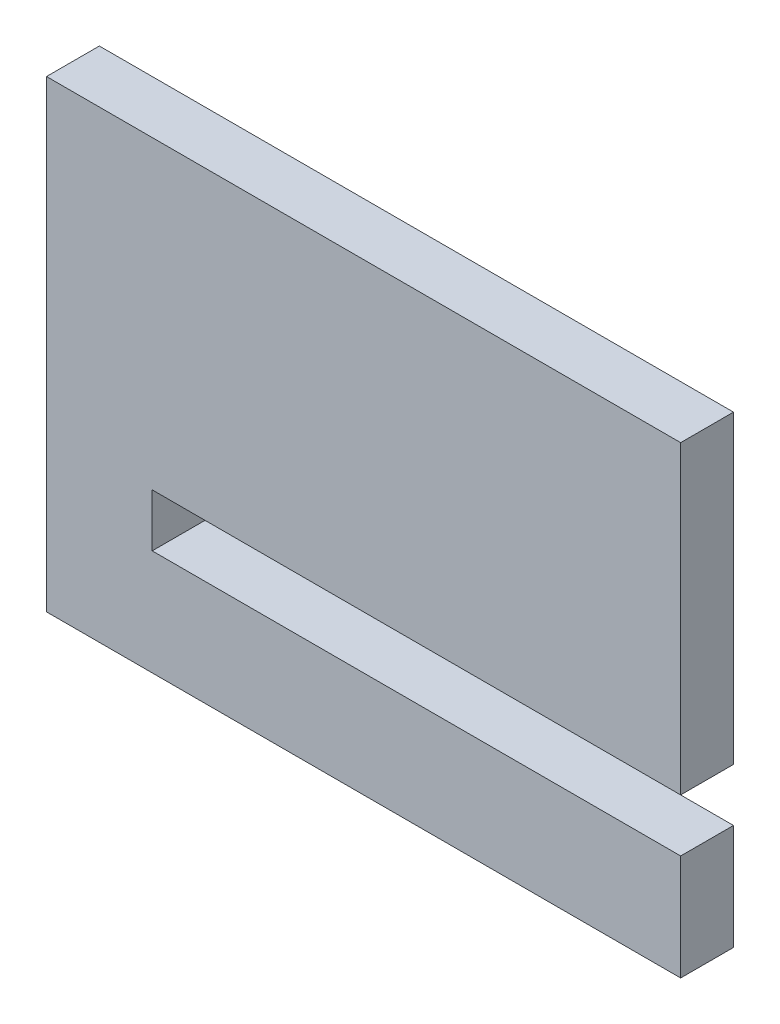
SolidWorks part; units mm, degrees
material "Pino"
ref_plane "Alzado" through (0, 0, 0) normal (0, 0, 1) x (1, 0, 0)
ref_plane "Planta" through (0, 0, 0) normal (0, 1, 0) x (1, 0, 0)
ref_plane "Vista lateral" through (0, 0, 0) normal (1, 0, 0) x (0, 0, -1)
sketch "Croquis1" plane through (0, 0, 0) normal (0, 1, 0) x (1, 0, 0)
  line L1 (-152.4, -12.7) -> (152.4, -12.7)
  line L2 (-152.4, -12.7) -> (-152.4, 12.7)
  line L3 (-152.4, 12.7) -> (152.4, 12.7)
  line L4 (152.4, -12.7) -> (152.4, 12.7)
  line L5 (-152.4, -12.7) -> (152.4, 12.7) construction
  line L6 (-152.4, 12.7) -> (152.4, -12.7) construction
  point P0 (0, 0)
  dimension "D1" = 25.4
  dimension "D2" = 304.8
extrude "Saliente-Extruir1" add sketch "Croquis1" along normal blind 50.8
sketch "Sketch1" plane through (0, 0, 12.7) normal (0, 0, 1) x (1, 0, 0)
  line L0 (-152.4, 50.8) -> (-152.4, 152.4)
  line L1 (-152.4, 152.4) -> (-101.6, 152.4)
  line L2 (-101.6, 152.4) -> (-101.6, 50.8)
  line L3 (-152.4, 50.8) -> (152.4, 50.8) construction
  line L4 (-101.6, 50.8) -> (-152.4, 50.8)
  dimension "D1" = 50.8
  dimension "D2" = 101.6
extrude "Boss-Extrude1" add sketch "Sketch1" against normal up to surface (25.4 mm away) up to face at (0, 25.4, -12.7)
sketch "Sketch2" plane through (0, 0, 12.7) normal (0, 0, 1) x (1, 0, 0)
  line L4 (152.4, 431.8) -> (152.4, -25.4) construction
  line L5 (152.4, 222.85) -> (152.4, 76.2)
  line L9 (-101.6, 76.2) -> (152.4, 76.2)
  line L10 (-101.6, 76.2) -> (152.4, 76.2) construction
  line L11 (152.4, 222.85) -> (-152.4, 222.85)
  line L12 (-152.4, 431.8) -> (-152.4, -25.4) construction
  line L13 (-152.4, 222.85) -> (-152.4, 152.4)
  line L14 (-152.4, 152.4) -> (-101.6, 152.4)
  line L15 (-101.6, 152.4) -> (-101.6, 76.2)
extrude "Boss-Extrude2" add sketch "Sketch2" against normal up to surface (25.4 mm away) up to face at (-33.8667, 67.7333, -12.7)
